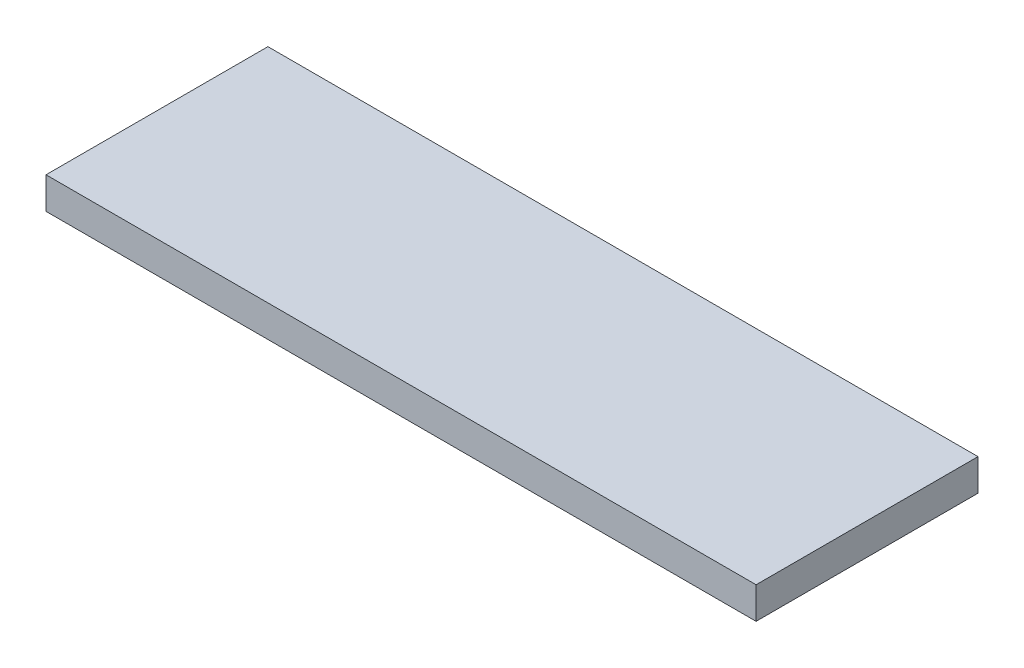
SolidWorks part; units mm, degrees
ref_plane "前视基准面" through (0, 0, 0) normal (0, 0, 1) x (1, 0, 0)
ref_plane "上视基准面" through (0, 0, 0) normal (0, 1, 0) x (1, 0, 0)
ref_plane "右视基准面" through (0, 0, 0) normal (1, 0, 0) x (0, 0, -1)
sketch "草图2" plane through (0, 0, 0) normal (0, 1, 0) x (1, 0, 0)
  line L1 (112, 35) -> (-112, 35)
  line L2 (112, 35) -> (112, -35)
  line L3 (112, -35) -> (-112, -35)
  line L4 (-112, 35) -> (-112, -35)
  line L5 (112, 35) -> (-112, -35) construction
  line L6 (112, -35) -> (-112, 35) construction
  point P0 (0, 0)
  dimension "D1" = 70
  dimension "D2" = 224
extrude "凸台-拉伸1" add sketch "草图2" along normal blind 10
sketch "草图3" plane through (0, 10, 0) normal (0, 1, 0) x (1, 0, 0)
  line L0 (0, 35) -> (0, -35) construction
  line L1 (112, 35) -> (-112, 35) construction
  line L2 (-112, -35) -> (112, -35) construction
